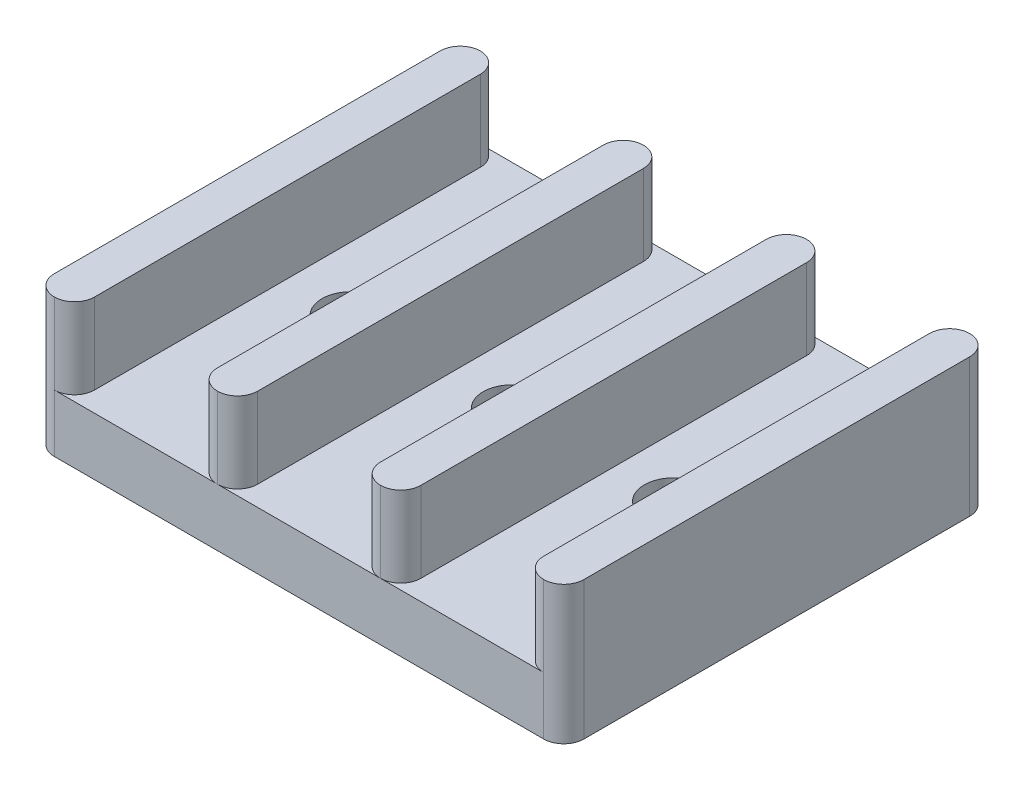
SolidWorks part; units mm, degrees
ref_plane "Front Plane" through (0, 0, 0) normal (0, 0, 1) x (1, 0, 0)
ref_plane "Top Plane" through (0, 0, 0) normal (0, 1, 0) x (1, 0, 0)
ref_plane "Right Plane" through (0, 0, 0) normal (1, 0, 0) x (0, 0, -1)
sketch "Sketch1" plane through (0, 0, 0) normal (0, 1, 0) x (1, 0, 0)
  line L1 (21.601, -14.8954) -> (-24.399, -14.8954)
  line L2 (21.601, -14.8954) -> (21.601, 22.1046)
  line L3 (21.601, 22.1046) -> (-24.399, 22.1046)
  line L4 (-24.399, -14.8954) -> (-24.399, 22.1046)
  circle A0 centre (-1.399, 3.6046) radius 2.5
  circle A1 centre (-15.399, 3.6046) radius 2.5
  circle A3 centre (12.601, 3.6046) radius 2.5
  dimension "D3" = 5
  dimension "D4" = 14
  dimension "D5" = 18.5
  dimension "D6" = 18.5
  dimension "D7" = 5
  dimension "D8" = 14
  dimension "D9" = 18.5
  dimension "D10" = 9
  dimension "D1" = 46
  dimension "D2" = 37
extrude "Boss-Extrude1" add sketch "Sketch1" along normal blind 12
sketch "Sketch2" plane through (0, 12, 0) normal (0, 1, 0) x (1, 0, 0)
  line L0 (-24.399, -14.8954) -> (21.601, -14.8954) construction
  line L1 (-24.399, 22.1046) -> (-20.899, 22.1046)
  line L2 (-24.399, 22.1046) -> (-24.399, -14.8954)
  line L3 (-24.399, -14.8954) -> (-20.899, -14.8954)
  line L4 (-20.899, 22.1046) -> (-20.899, -14.8954)
  line L5 (-10.2324, 22.1046) -> (-10.2324, -14.8954)
  line L6 (-10.2324, 22.1046) -> (-6.7324, 22.1046)
  line L7 (-6.7324, 22.1046) -> (-6.7324, -14.8954)
  line L8 (-10.2324, -14.8954) -> (-6.7324, -14.8954)
  line L9 (3.9342, 22.1046) -> (3.9342, -14.8954)
  line L10 (3.9342, 22.1046) -> (7.4342, 22.1046)
  line L11 (7.4342, 22.1046) -> (7.4342, -14.8954)
  line L12 (3.9342, -14.8954) -> (7.4342, -14.8954)
  line L13 (18.1008, 22.1046) -> (18.1008, -14.8954)
  line L14 (18.1008, 22.1046) -> (21.6008, 22.1046)
  line L15 (21.6008, 22.1046) -> (21.6008, -14.8954)
  line L16 (18.1008, -14.8954) -> (21.6008, -14.8954)
  line L18 (-24.399, 22.1046) -> (21.6008, 22.1046)
  line L19 (-24.399, 22.1046) -> (-24.399, -14.8954)
  line L20 (-24.399, -14.8954) -> (21.6008, -14.8954)
  line L21 (21.6008, 22.1046) -> (21.6008, -14.8954)
  circle M9 centre (-15.399, 3.6046) radius 2.5
  line M11 (21.601, 22.1046) -> (-24.399, 22.1046)
  line M13 (-24.399, -14.8954) -> (21.601, -14.8954)
  circle M14 centre (-1.399, 3.6046) radius 2.5
  circle M15 centre (12.601, 3.6046) radius 2.5
  dimension "D1" = 3.5
  dimension "D2" = 4
extrude "Cut-Extrude1" cut sketch "Sketch2" against normal blind 7 contours L5 L4 M11 M13 M9 | L9 L7 M11 M13 M14 | L13 L11 M11 M13 M15 region at (-15.5657, 12, -21.7196) region at (-1.3991, 12, -21.7196) region at (12.7675, 12, -21.7196)
fillet "Fillet1" radius 1.75 16 edges at (-24.399, 6, -22.1046) (21.601, 6, -22.1046) (21.601, 6, 14.8954) (-24.399, 6, 14.8954) (3.9342, 8.5, -22.1046) (-10.2324, 8.5, -22.1046) (-6.7324, 8.5, 14.8954) (-10.2324, 8.5, 14.8954) (3.9342, 8.5, 14.8954) (7.4342, 8.5, 14.8954) (7.4342, 8.5, -22.1046) (-6.7324, 8.5, -22.1046) (-20.899, 8.5, -22.1046) (-20.899, 8.5, 14.8954) (18.1008, 8.5, -22.1046) (18.1008, 8.5, 14.8954)
